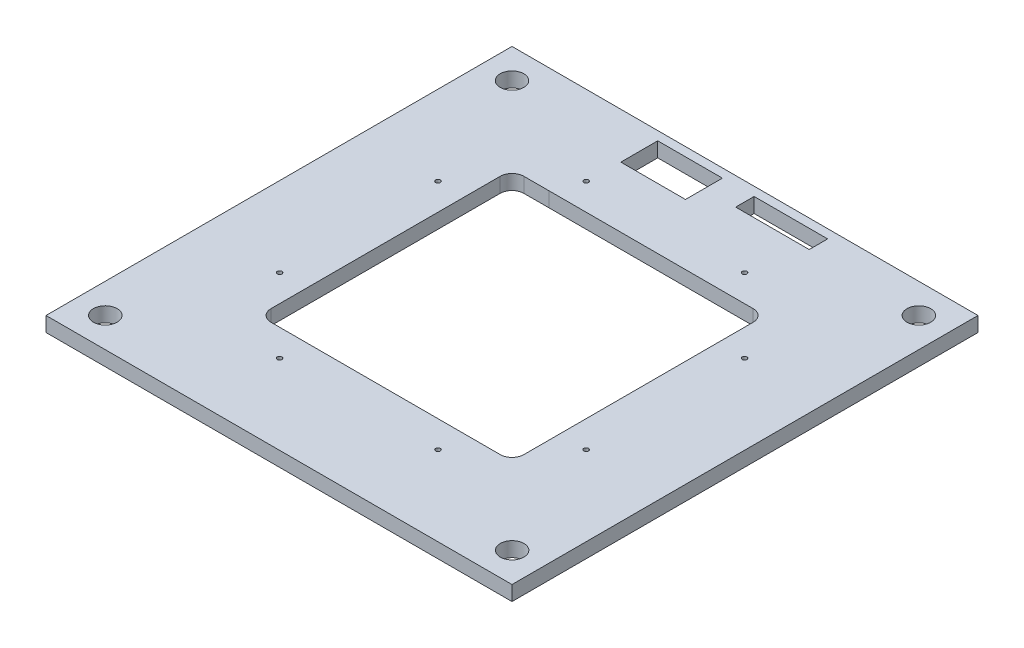
SolidWorks part; units mm, degrees
ref_plane "Front Plane" through (0, 0, 0) normal (0, 0, 1) x (1, 0, 0)
ref_plane "Top Plane" through (0, 0, 0) normal (0, 1, 0) x (1, 0, 0)
ref_plane "Right Plane" through (0, 0, 0) normal (1, 0, 0) x (0, 0, -1)
sketch "Sketch1" plane through (0, 0, 0) normal (0, 1, 0) x (1, 0, 0)
  line L0 (-100.0125, 99.9889) -> (-87.3125, 99.9889) construction
  line L1 (-100.0125, -100.0361) -> (100.0125, -100.0361)
  line L2 (-100.0125, -100.0361) -> (-100.0125, 99.9889)
  line L3 (-100.0125, 99.9889) -> (100.0125, 99.9889)
  line L4 (100.0125, -100.0361) -> (100.0125, 99.9889)
  line L5 (-100.0125, -100.0361) -> (100.0125, 99.9889) construction
  line L6 (-100.0125, 99.9889) -> (100.0125, -100.0361) construction
  line L7 (-74.6125, -74.6125) -> (74.6125, -74.6125) construction
  line L8 (-74.6125, -74.6125) -> (-74.6125, 74.6125) construction
  line L9 (-74.6125, 74.6125) -> (74.6125, 74.6125) construction
  line L10 (74.6125, -74.6125) -> (74.6125, 74.6125) construction
  line L11 (-74.6125, -74.6125) -> (74.6125, 74.6125) construction
  line L12 (-74.6125, 74.6125) -> (74.6125, -74.6125) construction
  line L13 (-87.3125, 99.9889) -> (-87.3125, -100.0361) construction
  line L14 (0, -55) -> (0, 55) construction
  line L15 (-55, 0) -> (55, 0) construction
  line L16 (-100.0125, 96.1789) -> (100.0125, 96.1789) construction
  line L18 (-33.6459, 96.1789) -> (-5.887, 96.1789)
  line L19 (-33.6459, 96.1789) -> (-33.6459, 80.3284)
  line L20 (-33.6459, 80.3284) -> (-5.887, 80.3284)
  line L21 (-5.887, 96.1789) -> (-5.887, 80.3284)
  line L22 (7.7239, 96.1789) -> (39.2871, 96.1789)
  line L23 (7.7239, 96.1789) -> (7.7239, 88.2654)
  line L24 (7.7239, 88.2654) -> (39.2871, 88.2654)
  line L25 (39.2871, 96.1789) -> (39.2871, 88.2654)
  line L33 (54.27, -38.5) -> (54.27, 38.5)
  line L47 (54.27, -38.5) -> (54.27, -42.77)
  line L54 (42.77, -54.27) -> (38.5, -54.27)
  line L55 (-34, 65.795) -> (34, -65.795) construction
  line L56 (38.5, -54.27) -> (-38.5, -54.27)
  line L57 (-42.77, -54.27) -> (-38.5, -54.27)
  line L59 (-34, -65.795) -> (34, 65.795) construction
  line L64 (38.5, 54.27) -> (54.2936, 54.27)
  line L67 (-54.27, -38.5) -> (-54.27, 38.5)
  line L69 (54.2936, 54.27) -> (54.27, 38.5)
  line L70 (49, -49) -> (-49, 49) construction
  line L71 (49, 49) -> (-49, -49) construction
  line L72 (42.77, -54.27) -> (54.2464, -54.27)
  line L73 (54.2464, -54.27) -> (54.27, -42.77)
  line L74 (-54.27, 38.5) -> (-54.27, 54.2464)
  line L75 (-54.27, 54.2464) -> (-38.5, 54.27)
  line L76 (0, 53) -> (0, -53) construction
  line L78 (-54.27, -38.5) -> (-54.27, -54.2936)
  line L83 (-54.27, -54.2936) -> (-42.77, -54.27)
  line L86 (-38.5, 54.27) -> (38.5, 54.27)
  circle A0 centre (-87.3125, 87.2889) radius 5.08
  circle A1 centre (87.3125, 87.2889) radius 5.08
  circle A2 centre (-87.3125, -87.2889) radius 5.08
  circle A3 centre (87.3125, -87.2889) radius 5.08
  circle A4 centre (34, 65.795) radius 1
  circle A5 centre (-34, 65.795) radius 1
  circle A6 centre (65.795, 34) radius 1
  circle A7 centre (65.795, -34) radius 1
  circle A8 centre (34, -65.795) radius 1
  circle A9 centre (-34, -65.795) radius 1
  circle A10 centre (-65.795, 34) radius 1
  circle A11 centre (-65.795, -34) radius 1
  point P6 (0, 54.27)
  point P11 (-87.3125, 87.2889)
  point P60 (0, -54.27)
  dimension "D5" = 10.16
  dimension "D7" = 85.54
  dimension "D1" = 200.025
  dimension "D2" = 200.025
  dimension "D3" = 149.225
  dimension "D4" = 12.7
  dimension "D6" = 3.81
extrude "Boss-Extrude1" add sketch "Sketch1" along normal blind 6.35
fillet "Fillet1" radius 5.08 4 edges at (54.2464, 3.175, 54.27) (-54.27, 3.175, 54.2936) (54.2936, 3.175, -54.27) (-54.27, 3.175, -54.2464)
sketch "Sketch2" plane through (0, 6.35, 0) normal (0, 1, 0) x (1, 0, 0)
  line L4 (-100.0125, -100.0361) -> (100.0125, -100.0361)
  line L5 (100.0125, -100.0361) -> (100.0125, 99.9889)
  line L6 (100.0125, 99.9889) -> (-100.0125, 99.9889)
  line L7 (-100.0125, 99.9889) -> (-100.0125, -100.0361)
  line L8 (-100.0125, -100.0361) -> (100.0125, -100.0361)
  line L9 (100.0125, -100.0361) -> (100.0125, 99.9889)
  line L10 (100.0125, 99.9889) -> (-100.0125, 99.9889)
  line L11 (-100.0125, 99.9889) -> (-100.0125, -100.0361)
  line L12 (-5.887, 96.1789) -> (-33.6459, 96.1789)
  line L13 (-5.887, 80.3284) -> (-5.887, 96.1789)
  line L14 (-33.6459, 80.3284) -> (-5.887, 80.3284)
  line L15 (-33.6459, 96.1789) -> (-33.6459, 80.3284)
  line L16 (-5.887, 96.1789) -> (-33.6459, 96.1789)
  line L17 (-5.887, 80.3284) -> (-5.887, 96.1789)
  line L18 (-33.6459, 80.3284) -> (-5.887, 80.3284)
  line L19 (-33.6459, 96.1789) -> (-33.6459, 80.3284)
  line L20 (39.2871, 96.1789) -> (7.7239, 96.1789)
  line L21 (39.2871, 88.2654) -> (39.2871, 96.1789)
  line L22 (7.7239, 88.2654) -> (39.2871, 88.2654)
  line L23 (7.7239, 96.1789) -> (7.7239, 88.2654)
  line L24 (39.2871, 96.1789) -> (7.7239, 96.1789)
  line L25 (39.2871, 88.2654) -> (39.2871, 96.1789)
  line L26 (7.7239, 88.2654) -> (39.2871, 88.2654)
  line L27 (7.7239, 96.1789) -> (7.7239, 88.2654)
  line L39 (-38.5, 54.27) -> (-54.27, 54.2464)
  line L40 (-54.27, 54.2464) -> (-54.27, 38.5)
  line L41 (-54.27, 38.5) -> (-54.27, -38.5)
  line L42 (-54.27, -38.5) -> (-54.27, -54.2936)
  line L43 (-54.27, -54.2936) -> (-42.77, -54.27)
  line L44 (-42.77, -54.27) -> (-38.5, -54.27)
  line L45 (-38.5, -54.27) -> (38.5, -54.27)
  line L46 (38.5, -54.27) -> (42.77, -54.27)
  line L47 (42.77, -54.27) -> (54.2464, -54.27)
  line L48 (54.2464, -54.27) -> (54.27, -42.77)
  line L49 (54.27, -42.77) -> (54.27, -38.5)
  line L50 (54.27, -38.5) -> (54.27, 38.5)
  line L51 (54.27, 38.5) -> (54.2936, 54.27)
  line L52 (54.2936, 54.27) -> (38.5, 54.27)
  line L53 (38.5, 54.27) -> (-38.5, 54.27)
  line L54 (-38.5, 54.27) -> (-49.1976, 54.254)
  line L55 (-54.27, 49.174) -> (-54.27, 38.5)
  line L56 (-54.27, 38.5) -> (-54.27, -38.5)
  line L57 (-54.27, -38.5) -> (-54.27, -49.2032)
  line L58 (-49.1796, -54.2832) -> (-42.77, -54.27)
  line L59 (-42.77, -54.27) -> (-38.5, -54.27)
  line L60 (-38.5, -54.27) -> (38.5, -54.27)
  line L61 (38.5, -54.27) -> (42.77, -54.27)
  line L62 (42.77, -54.27) -> (49.1768, -54.27)
  line L63 (54.2568, -49.2004) -> (54.27, -42.77)
  line L64 (54.27, -42.77) -> (54.27, -38.5)
  line L65 (54.27, -38.5) -> (54.27, 38.5)
  line L66 (54.27, 38.5) -> (54.286, 49.1824)
  line L67 (49.206, 54.27) -> (38.5, 54.27)
  line L68 (38.5, 54.27) -> (-38.5, 54.27)
  arc A0 (-54.27, -49.2032) -> (-49.1796, -54.2832) centre (-49.19, -49.2032) ccw construction
  circle A1 centre (-87.3125, 87.2889) radius 5.08
  circle A2 centre (-87.3125, 87.2889) radius 5.08
  circle A3 centre (87.3125, -87.2889) radius 5.08
  circle A4 centre (87.3125, -87.2889) radius 5.08
  circle A5 centre (-87.3125, -87.2889) radius 5.08
  circle A6 centre (-87.3125, -87.2889) radius 5.08
  circle A7 centre (87.3125, 87.2889) radius 5.08
  circle A8 centre (87.3125, 87.2889) radius 5.08
  circle A9 centre (-65.795, -34) radius 1
  circle A10 centre (-65.795, -34) radius 1
  circle A11 centre (-65.795, 34) radius 1
  circle A12 centre (-65.795, 34) radius 1
  circle A13 centre (-34, -65.795) radius 1
  circle A14 centre (-34, -65.795) radius 1
  circle A15 centre (34, -65.795) radius 1
  circle A16 centre (34, -65.795) radius 1
  circle A17 centre (65.795, -34) radius 1
  circle A18 centre (65.795, -34) radius 1
  circle A19 centre (65.795, 34) radius 1
  circle A20 centre (65.795, 34) radius 1
  circle A21 centre (-34, 65.795) radius 1
  circle A22 centre (-34, 65.795) radius 1
  circle A23 centre (34, 65.795) radius 1
  circle A24 centre (34, 65.795) radius 1
  arc A25 (49.1768, -54.27) -> (54.2568, -49.2004) centre (49.1768, -49.19) ccw construction
  arc A26 (-49.1976, 54.254) -> (-54.27, 49.174) centre (-49.19, 49.174) ccw construction
  arc A27 (54.286, 49.1824) -> (49.206, 54.27) centre (49.206, 49.19) ccw construction
  arc A28 (49.1768, -54.27) -> (54.2568, -49.2004) centre (49.1768, -49.19) ccw
  arc A29 (-54.27, -49.2032) -> (-49.1796, -54.2832) centre (-49.19, -49.2032) ccw
  arc A30 (-49.1976, 54.254) -> (-54.27, 49.174) centre (-49.19, 49.174) ccw
  arc A31 (54.286, 49.1824) -> (49.206, 54.27) centre (49.206, 49.19) ccw
  dimension "D1" = 0
  dimension "D2" = 0
  dimension "D3" = 0
  dimension "D4" = 0
  dimension "D5" = 0
  dimension "D6" = 0
  dimension "D7" = 0
  dimension "D8" = 0
  dimension "D9" = 0
  dimension "D10" = 0
  dimension "D11" = 0
  dimension "D12" = 0
  dimension "D13" = 0
  dimension "D14" = 0
  dimension "D15" = 0
  dimension "D16" = 0
